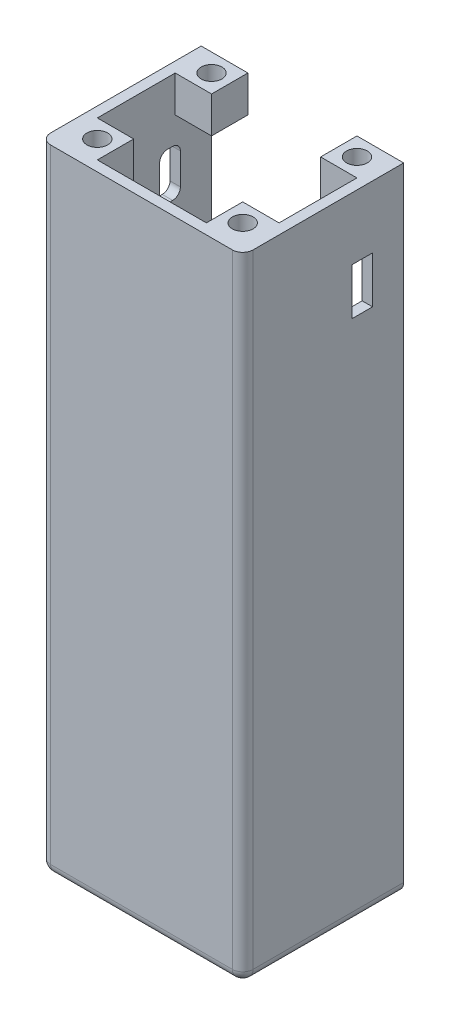
SolidWorks part; units mm, degrees
ref_plane "Front Plane" through (0, 0, 0) normal (0, 0, 1) x (1, 0, 0)
ref_plane "Top Plane" through (0, 0, 0) normal (0, 1, 0) x (1, 0, 0)
ref_plane "Right Plane" through (0, 0, 0) normal (1, 0, 0) x (0, 0, -1)
sketch "Sketch1" plane through (0, 0, 0) normal (0, 0, 1) x (1, 0, 0)
  line L0 (0, 0) -> (0, 122)
  line L1 (0, 122) -> (39, 122)
  line L2 (39, 122) -> (39, 0)
  line L3 (39, 0) -> (0, 0)
  dimension "D1" = 122
  dimension "3.9cm" = 39
extrude "Boss-Extrude2" add sketch "Sketch1" along normal blind 2
sketch "Sketch2" plane through (0, 0, 0) normal (0, 0, -1) x (-1, 0, 0)
  line L0 (-39, 122) -> (-37, 122)
  line L1 (-39, 122) -> (0, 122) construction
  line L2 (-37, 122) -> (-37, 0)
  line L3 (0, 0) -> (-39, 0) construction
  line L4 (-37, 0) -> (-39, 0)
  line L5 (-39, 0) -> (-39, 122)
  dimension "D1" = 2
extrude "Boss-Extrude3" add sketch "Sketch2" along normal blind 25
sketch "Sketch3" plane through (0, 0, 0) normal (0, 0, -1) x (-1, 0, 0)
  line L0 (0, 122) -> (0, 0)
  line L1 (0, 0) -> (-2, 0)
  line L2 (0, 0) -> (-37, 0) construction
  line L3 (-2, 0) -> (-2, 122)
  line L4 (-37, 122) -> (0, 122) construction
  line L5 (-2, 122) -> (0, 122)
  dimension "D1" = 2
extrude "Boss-Extrude4" add sketch "Sketch3" along normal blind 25
sketch "Sketch4" plane through (0, 0, 0) normal (0, 0, -1) x (-1, 0, 0)
  line L0 (-37, 0) -> (-2, 0)
  line L1 (-2, 0) -> (-2, 2)
  line L2 (-2, 122) -> (-2, 0) construction
  line L3 (-2, 2) -> (-37, 2)
  line L4 (-37, 0) -> (-37, 122) construction
  line L5 (-37, 2) -> (-37, 0)
  dimension "D1" = 2
extrude "Boss-Extrude5" add sketch "Sketch4" along normal blind 25
fillet "Fillet2" radius 2 3 edges at (0, 0, -11.5) (19.5, 0, 2) (39, 0, -11.5)
ref_plane "Plane1" through (39, 0, 0) normal (1, 0, 0) x (0, 0, -1)
sketch "Sketch5" plane through (39, 0, 0) normal (1, 0, 0) x (0, 0, -1)
  line L0 (23, 110) -> (23, 101)
  line L1 (23, 101) -> (19, 101)
  line L2 (19, 101) -> (19, 110)
  line L3 (19, 110) -> (23, 110)
  line L4 (-2, 2) -> (25, 2) construction
  line L5 (-2, 122) -> (25, 122) construction
  line L6 (-2, 2) -> (-2, 122) construction
  dimension "D1" = 99
  dimension "D2" = 9
  dimension "D3" = 12
  dimension "D4" = 4
  dimension "D5" = 25
sketch "Sketch6" plane through (0, 0, -25) normal (0, 0, -1) x (-1, 0, 0)
  line L0 (-2, 122) -> (0, 122)
  line L1 (0, 122) -> (0, 2)
  line L2 (-2, 0) -> (-37, 0)
  line L3 (-39, 14.85) -> (-39, -14.85) construction
  line L4 (-39, 2) -> (-39, 122)
  line L5 (-39, 122) -> (-37, 122)
  line L6 (-37, 122) -> (-37, 2)
  line L7 (-37, 2) -> (-2, 2)
  line L8 (-2, 2) -> (-2, 122)
  arc A0 (0, 2) -> (-2, 0) centre (-2, 2) cw
  arc A1 (-37, 0) -> (-39, 2) centre (-37, 2) cw
extrude "Boss-Extrude7" add sketch "Sketch6" along normal blind 4
ref_plane "Plane2" through (0, 0, 0) normal (-1, 0, 0) x (0, 0, 1)
sketch "Sketch7" plane through (0, 0, 0) normal (-1, 0, 0) x (0, 0, 1)
  line L0 (-21.5, 110) -> (-20.5, 110)
  line L1 (-19, 108.5) -> (-19, 102.5)
  line L2 (-20.5, 101) -> (-21.5, 101)
  line L3 (-23, 102.5) -> (-23, 108.5)
  arc A0 (-20.5, 101) -> (-19, 102.5) centre (-20.5, 102.5) ccw
  arc A1 (-23, 102.5) -> (-21.5, 101) centre (-21.5, 102.5) ccw
  arc A2 (-20.5, 110) -> (-19, 108.5) centre (-20.5, 108.5) cw
  arc A3 (-23, 108.5) -> (-21.5, 110) centre (-21.5, 108.5) cw
  point P10 (-19, 101)
  point P13 (-23, 101)
  point P16 (-19, 110)
  point P19 (-23, 110)
  dimension "D1" = 1.5
extrude "Cut-Extrude2" cut sketch "Sketch7" against normal blind 4
extrude "Cut-Extrude3" cut sketch "Sketch5" against normal blind 4
fillet "Fillet4" radius 2 4 edges at (38.4142, 0.5858, 1.4142) (0.5858, 0.5858, 1.4142) (39, 62, 2) (0, 62, 2)
ref_plane "Plane3" through (0, 0, -29) normal (0, 0, -1) x (-1, 0, 0)
sketch "Sketch8" plane through (0, 0, -29) normal (0, 0, -1) x (-1, 0, 0)
  line L1 (-37, 2) -> (-30, 2)
  line L2 (-37, 2) -> (-37, 9)
  line L3 (-37, 9) -> (-30, 9)
  line L4 (-30, 2) -> (-30, 9)
  dimension "D1" = 7
  dimension "D2" = 7
  dimension "D3" = 7
extrude "Boss-Extrude8" add sketch "Sketch8" against normal blind 7
sketch "Sketch9" plane through (0, 0, -29) normal (0, 0, -1) x (-1, 0, 0)
  line L1 (-2, 2) -> (-9, 2)
  line L2 (-2, 2) -> (-2, 9)
  line L3 (-2, 9) -> (-9, 9)
  line L4 (-9, 2) -> (-9, 9)
  dimension "D1" = 7
  dimension "D2" = 7
extrude "Boss-Extrude10" add sketch "Sketch9" against normal blind 7
sketch "Sketch10" plane through (0, 0, -29) normal (0, 0, -1) x (-1, 0, 0)
  circle A0 centre (-33.5, 5.5) radius 2
  circle A1 centre (-5.5, 5.5) radius 2
  dimension "D1" = 4
  dimension "D2" = 4
extrude "Cut-Extrude6" cut sketch "Sketch10" against normal blind 7
ref_plane "Plane4" through (0, 122, 0) normal (0, 1, 0) x (1, 0, 0)
sketch "Sketch11" plane through (0, 122, 0) normal (0, 1, 0) x (1, 0, 0)
  line L0 (21.45, 29) -> (-21.45, 29) construction
  line L1 (2, 0) -> (9, 0)
  line L2 (2, 0) -> (2, 7)
  line L3 (2, 7) -> (9, 7)
  line L4 (9, 0) -> (9, 7)
  line L5 (37, 0) -> (30, 0)
  line L6 (37, 0) -> (37, 7)
  line L7 (37, 7) -> (30, 7)
  line L8 (30, 0) -> (30, 7)
  line L9 (2, 22) -> (9, 22)
  line L10 (2, 22) -> (2, 29)
  line L11 (2, 29) -> (9, 29)
  line L12 (9, 22) -> (9, 29)
  line L13 (9, 22) -> (9, 29) construction
  line L14 (37, 22) -> (37, 29) construction
  line L15 (30, 22) -> (37, 22)
  line L16 (30, 22) -> (30, 29)
  line L17 (30, 29) -> (37, 29)
  line L18 (37, 22) -> (37, 29)
  dimension "D1" = 7
  dimension "D2" = 7
  dimension "D3" = 7
  dimension "D4" = 7
  dimension "D5" = 7
  dimension "D6" = 7
  dimension "D7" = 7
  dimension "D8" = 7
extrude "Boss-Extrude11" add sketch "Sketch11" against normal blind 7
sketch "Sketch12" plane through (0, 122, 0) normal (0, 1, 0) x (1, 0, 0)
  circle A0 centre (5.5, 25.5) radius 2
  circle A1 centre (33.5, 25.5) radius 2
  circle A3 centre (5.5, 3.5) radius 2
  circle A4 centre (33.5, 3.5) radius 2
  dimension "D1" = 4
  dimension "D2" = 4
  dimension "D3" = 4
  dimension "D4" = 4
extrude "Cut-Extrude7" cut sketch "Sketch12" against normal blind 7
